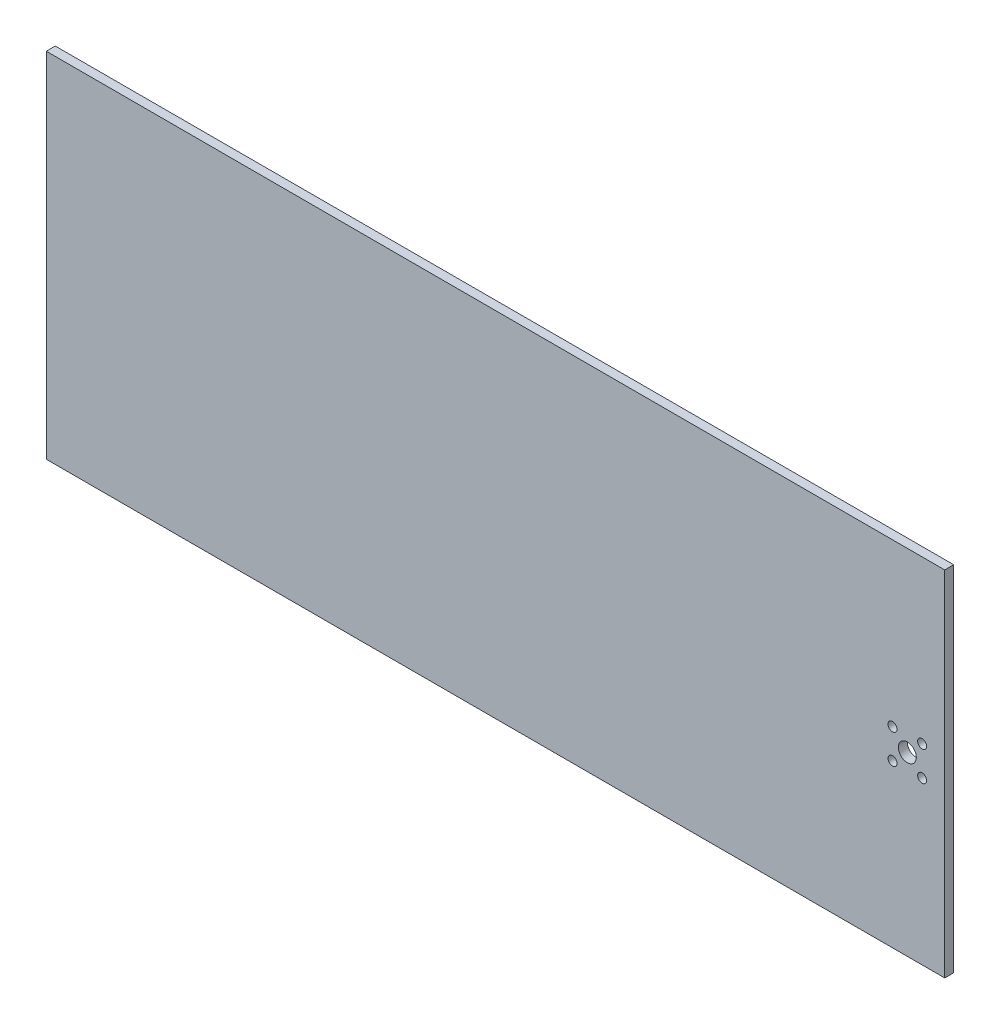
SolidWorks part; units mm, degrees
ref_plane "前视基准面" through (0, 0, 0) normal (0, 0, 1) x (1, 0, 0)
ref_plane "上视基准面" through (0, 0, 0) normal (0, 1, 0) x (1, 0, 0)
ref_plane "右视基准面" through (0, 0, 0) normal (1, 0, 0) x (0, 0, -1)
other "Configuration Table"
sketch "草图1" plane through (0, 0, 0) normal (0, 0, 1) x (1, 0, 0)
  line L1 (150, -59) -> (-150, -59)
  line L2 (150, -59) -> (150, 59)
  line L3 (150, 59) -> (-150, 59)
  line L4 (-150, -59) -> (-150, 59)
  line L5 (150, -59) -> (-150, 59) construction
  line L6 (150, 59) -> (-150, -59) construction
  point P0 (0, 0)
  dimension "D1" = 118
  dimension "D2" = 300
extrude "凸台-拉伸1" add sketch "草图1" along normal blind 3
sketch "草图2" plane through (0, 0, 0) normal (0, 0, -1) x (-1, 0, 0)
  circle A0 centre (-142.4497, 4.9497) radius 1.5
  circle A1 centre (-132.5503, 4.9497) radius 1.5
  circle A2 centre (-137.5, 0) radius 3
  circle A3 centre (-142.4497, -4.9497) radius 1.5
  circle A4 centre (-132.5503, -4.9497) radius 1.5
extrude "切除-拉伸1" cut sketch "草图2" against normal blind 3
